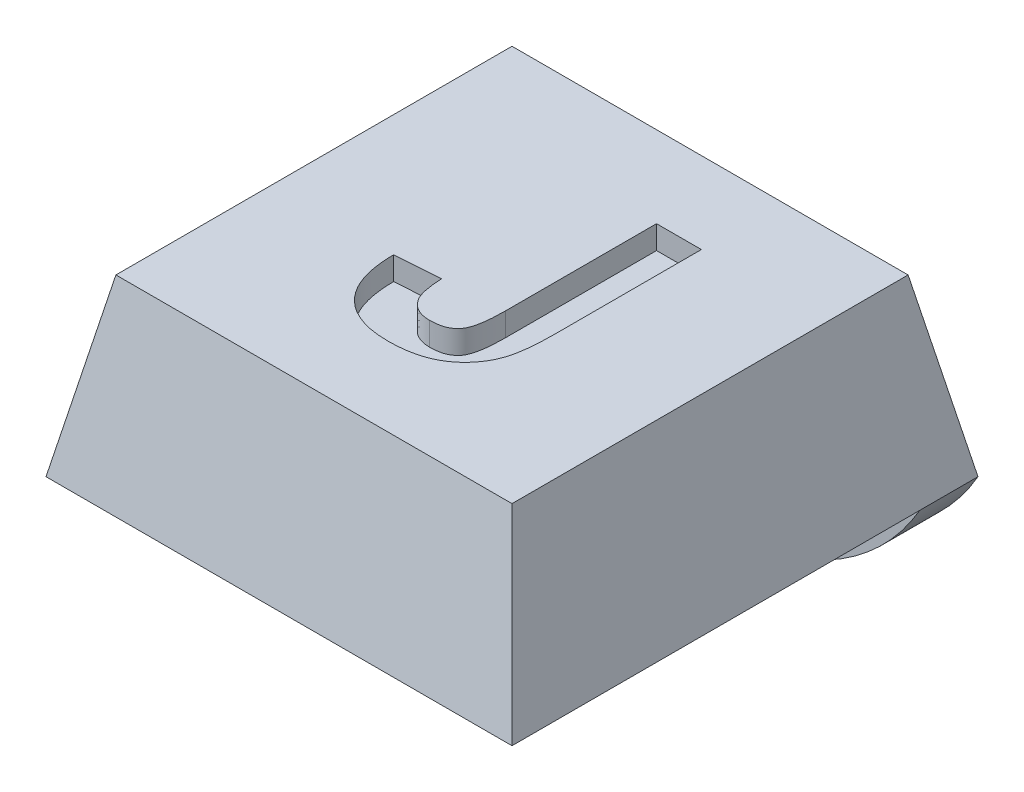
SolidWorks part; units mm, degrees
ref_plane "Front Plane" through (0, 0, 0) normal (0, 0, 1) x (1, 0, 0)
ref_plane "Top Plane" through (0, 0, 0) normal (0, 1, 0) x (1, 0, 0)
ref_plane "Right Plane" through (0, 0, 0) normal (1, 0, 0) x (0, 0, -1)
sketch "Sketch1" plane through (0, 0, 0) normal (0, 1, 0) x (1, 0, 0)
  line L1 (0, 0) -> (8, 0)
  line L2 (0, 0) -> (0, 8)
  line L3 (0, 8) -> (8, 8)
  line L4 (8, 0) -> (8, 8)
  dimension "D1" = 8
  dimension "D2" = 8
extrude "Boss-Extrude1" add sketch "Sketch1" along normal blind 3
sketch "Sketch2" plane through (0, 0, 0) normal (0, 0, 1) x (1, 0, 0)
  line L0 (0, 0) -> (0.6, 3)
  line L1 (0, 3) -> (8, 3) construction
  line L2 (0.6, 3) -> (0, 3)
  line L3 (0, 3) -> (0, 0)
  line L4 (8, 0) -> (7.4, 3)
  line L5 (7.4, 3) -> (8, 3)
  line L6 (8, 3) -> (8, 0)
  dimension "D1" = 0.6
  dimension "D2" = 0.6
extrude "Cut-Extrude1" cut sketch "Sketch2" against normal through all both and the other way through all
sketch "Sketch3" plane through (0, 0, 0) normal (1, 0, 0) x (0, 0, -1)
  line L0 (0, 0) -> (0.6, 3)
  line L1 (8, 3) -> (0, 3) construction
  line L2 (0.6, 3) -> (0, 3)
  line L3 (0, 3) -> (0, 0)
  line L4 (8, 3) -> (7.4, 3)
  line L5 (7.4, 3) -> (8, 0)
  line L6 (8, 3) -> (8, 0)
  dimension "D1" = 0.6
  dimension "D2" = 0.6
extrude "Cut-Extrude2" cut sketch "Sketch3" along normal blind 11
sketch "Sketch4" plane through (0, 0, 0) normal (0, -1, 0) x (1, 0, 0)
  line L0 (8, 0) -> (8, -8) construction
  line L3 (0, 0) -> (8, 0) construction
  circle A0 centre (4, -3.75) radius 1.8
  dimension "D1" = 3.6
  dimension "D2" = 4
  dimension "D3" = 3.75
extrude "Cut-Extrude3" cut sketch "Sketch4" against normal blind 0.8
sketch "Sketch5" plane through (0, 0, 0) normal (0, -1, 0) x (1, 0, 0)
  line L0 (8, 0) -> (8, -8) construction
  line L1 (0, -8) -> (8, -8)
  line L2 (0, -8) -> (0, -7)
  line L3 (0, -7) -> (8, -7)
  line L4 (8, -8) -> (8, -7)
  dimension "D1" = 1
extrude "Boss-Extrude2" add sketch "Sketch5" along normal blind 2
fillet "Fillet1" radius 4 2 edges at (8, -2, -7.5) (0, -2, -7.5)
sketch "Sketch6" plane through (0, 3, 0) normal (0, 1, 0) x (1, 0, 0)
  text T0 "J" font "Arial" height 4
extrude "Cut-Extrude4" cut sketch "Sketch6" against normal blind 0.4
